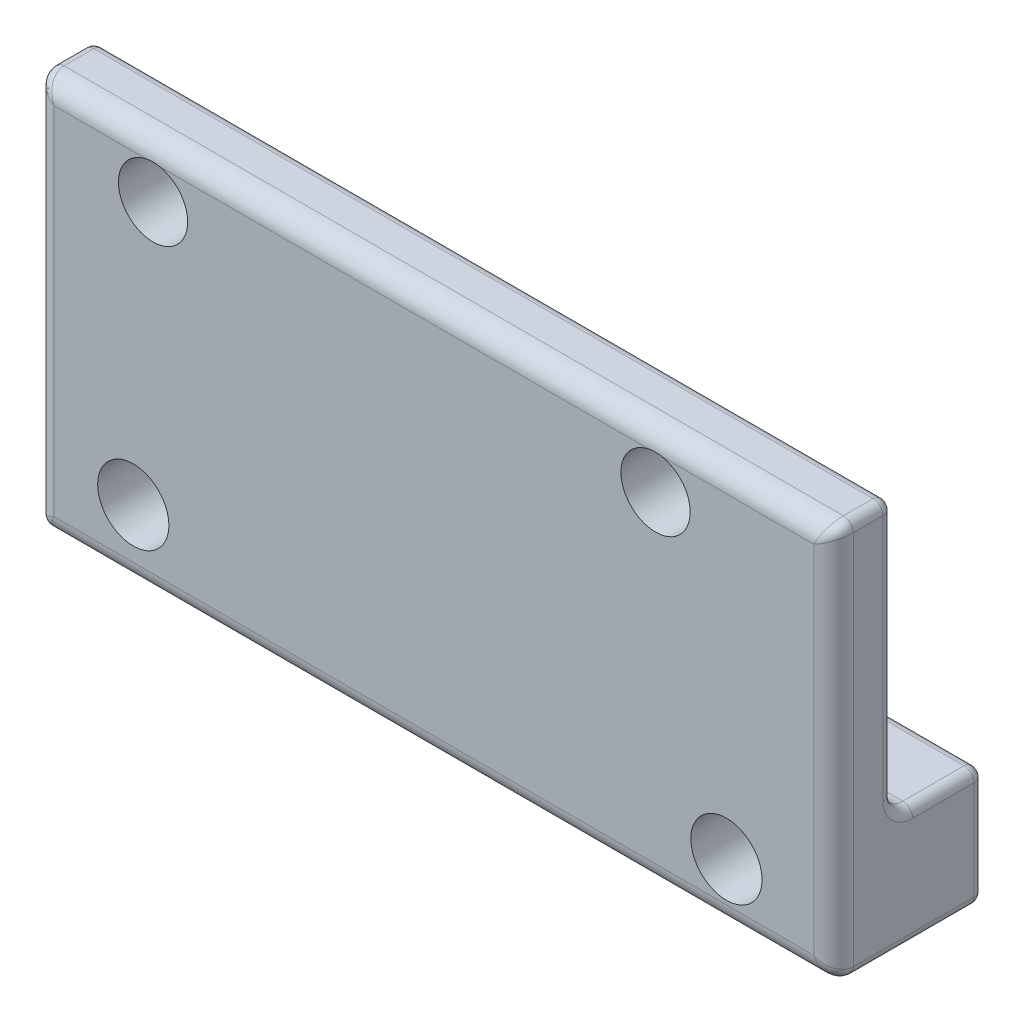
SolidWorks part; units mm, degrees
ref_plane "Front Plane" through (0, 0, 0) normal (0, 0, 1) x (1, 0, 0)
ref_plane "Top Plane" through (0, 0, 0) normal (0, 1, 0) x (1, 0, 0)
ref_plane "Right Plane" through (0, 0, 0) normal (1, 0, 0) x (0, 0, -1)
sketch "Sketch1" plane through (0, 0, 0) normal (0, 0, 1) x (1, 0, 0)
  line L1 (98.5893, 32.9709) -> (138, 32.9709)
  line L2 (98.0893, 32.4709) -> (98.0893, 12.9709)
  line L3 (98.0893, 12.9709) -> (138.5, 12.9709)
  line L4 (138.5, 32.4709) -> (138.5, 12.9709)
  circle A2 centre (129.5, 30.2538) radius 1.75
  arc A3 (98.5893, 32.9709) -> (98.0893, 32.4709) centre (98.5893, 32.4709) ccw
  circle A4 centre (104.0893, 30.2538) radius 1.75
  arc A5 (138, 32.9709) -> (138.5, 32.4709) centre (138, 32.4709) cw
  point P7 (138.5, 32.9709)
  dimension "D1" = 0.5
  dimension "D2" = 20
extrude "Boss-Extrude1" add sketch "Sketch1" along normal blind 3
sketch "Sketch3" plane through (0, 0, 0) normal (0, 0, -1) x (-1, 0, 0)
  line L1 (-138.5, 18.9709) -> (-98.0893, 18.9709)
  line L4 (-138.5, 32.4709) -> (-138.5, 12.9709)
  line L5 (-138.5, 12.9709) -> (-98.0893, 12.9709)
  line L6 (-98.0893, 12.9709) -> (-98.0893, 32.4709)
  line L7 (-98.5893, 32.9709) -> (-138, 32.9709)
  line L8 (-138.5, 18.9709) -> (-138.5, 12.9709)
  line L9 (-138.5, 12.9709) -> (-98.0893, 12.9709)
  line L10 (-98.0893, 12.9709) -> (-98.0893, 18.9709)
  arc A2 (-98.0893, 32.4709) -> (-98.5893, 32.9709) centre (-98.5893, 32.4709) ccw
  arc A3 (-138, 32.9709) -> (-138.5, 32.4709) centre (-138, 32.4709) ccw
  dimension "D2" = 6
  dimension "D1" = 0
extrude "Boss-Extrude2" add sketch "Sketch3" along normal blind 4.6
sketch "Sketch2" plane through (0, 0, 0) normal (0, 0, -1) x (-1, 0, 0)
  line L0 (-98.0893, 32.4709) -> (-98.0893, 12.9709) construction
  line L5 (-138, 32.9709) -> (-98.5893, 32.9709) construction
  circle A0 centre (-133.0848, 15.9709) radius 1.8
  circle A1 centre (-103.0893, 16.4899) radius 1.8
  dimension "D1" = 3.6
  dimension "D2" = 3.6
  dimension "D4" = 5
  dimension "D5" = 17
  dimension "D3" = 30
extrude "Cut-Extrude1" cut sketch "Sketch2" against normal through all and the other way through all
fillet "Fillet1" radius 1 7 edges at (138.5, 22.7209, 3) (138.3536, 32.8245, 3) (118.2946, 32.9709, 3) (98.2357, 32.8245, 3) (118.2946, 18.9709, 0) (98.0893, 22.7209, 3) (118.2946, 12.9709, 3)
fillet "Fillet2" radius 0.5 17 edges at (98.3822, 13.2638, 2.7071) (138.2071, 13.2638, 2.7071) (138.3536, 32.8245, 0) (98.2357, 32.8245, 0) (118.2946, 12.9709, -4.6) (98.0893, 15.9709, -4.6) (98.0893, 18.9709, -2.8) (98.0893, 19.2638, -0.2929) (98.0893, 26.2209, 0) (98.0893, 12.9709, -1.3) (138.5, 26.2209, 0) (138.5, 19.2638, -0.2929) (138.5, 18.9709, -2.8) (138.5, 15.9709, -4.6) (138.5, 12.9709, -1.3) (118.2946, 32.9709, 0) (118.2946, 18.9709, -4.6)
